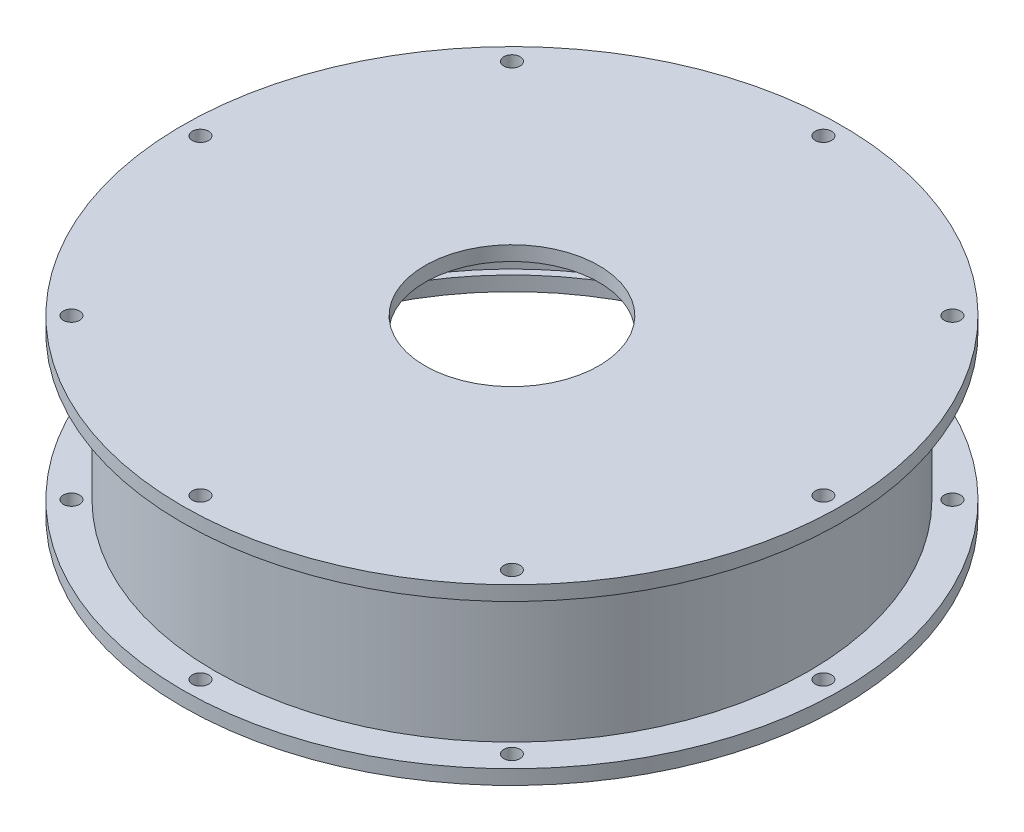
SolidWorks part; units mm, degrees
ref_plane "Front Plane" through (0, 0, 0) normal (0, 0, 1) x (1, 0, 0)
ref_plane "Top Plane" through (0, 0, 0) normal (0, 1, 0) x (1, 0, 0)
ref_plane "Right Plane" through (0, 0, 0) normal (1, 0, 0) x (0, 0, -1)
sketch "Sketch1" plane through (0, 0, 0) normal (0, 1, 0) x (1, 0, 0)
  circle A0 centre (0, 0) radius 144.4625
  dimension "D1" = 288.925
extrude "Boss-Extrude1" add sketch "Sketch1" along normal blind 6.35 contours A0
sketch "Sketch2" plane through (0, 6.35, 0) normal (0, 1, 0) x (1, 0, 0)
  circle A0 centre (0, 0) radius 136.525
  point P3 (0, 136.525)
  point P4 (96.5378, 96.5378)
  point P5 (136.525, 0)
  point P8 (96.5378, -96.5378)
  point P9 (0, -136.525)
  point P10 (-96.5378, -96.5378)
  point P11 (-136.525, 0)
  point P12 (-96.5378, 96.5378)
  dimension "D1" = 273.05
  dimension "D2" = 8
hole_wizard "1/4 Clearance Hole1" positions "Sketch2" profile "Sketch3" hole size "1/4" standard "ANSI Inch" end condition up to next
sketch "Sketch3" plane through (-96.5378, 6.35, -96.5378) normal (1, 0, 0) x (0, 0, 1)
  line L0 (0, 0) -> (0, 6.35)
  line L1 (0, 6.35) -> (3.5712, 6.35)
  line L2 (3.5712, 6.35) -> (3.5712, 0)
  line L5 (3.5712, 0) -> (0, 0)
  line L11 (0, -6.35) -> (0, 107.95) construction
  dimension "Thru Hole Dia." = 7.1425
  dimension "Thru Hole Depth" = 6.35
sketch "Sketch4" plane through (0, 6.35, 0) normal (0, 1, 0) x (1, 0, 0)
  circle A0 centre (0, 0) radius 130.175
  circle A1 centre (0, 0) radius 123.825
  dimension "D1" = 260.35
  dimension "D2" = 247.65
extrude "Boss-Extrude2" add sketch "Sketch4" along normal blind 63.5
ref_plane "Plane1" through (0, 72.39, 0) normal (0, 1, 0) x (1, 0, 0)
ref_plane "Plane3" through (0, 38.1, 0) normal (0, 1, 0) x (1, 0, 0)
mirror "Mirror2" about plane through (0, 38.1, 0) normal (0, 1, 0) of "Boss-Extrude1"
mirror "Mirror3" about plane through (0, 38.1, 0) normal (0, 1, 0) of "1/4 Clearance Hole1"
sketch "Sketch7" plane through (0, 0, 0) normal (0, -1, 0) x (1, 0, 0)
  circle A0 centre (0, 0) radius 120.65
  dimension "D1" = 241.3
extrude "Cut-Extrude1" cut sketch "Sketch7" against normal blind 69.85
sketch "Sketch8" plane through (0, 76.2, 0) normal (0, 1, 0) x (1, 0, 0)
  circle A0 centre (0, 0) radius 38.1
  dimension "D1" = 76.2
extrude "Cut-Extrude2" cut sketch "Sketch8" against normal up to next
